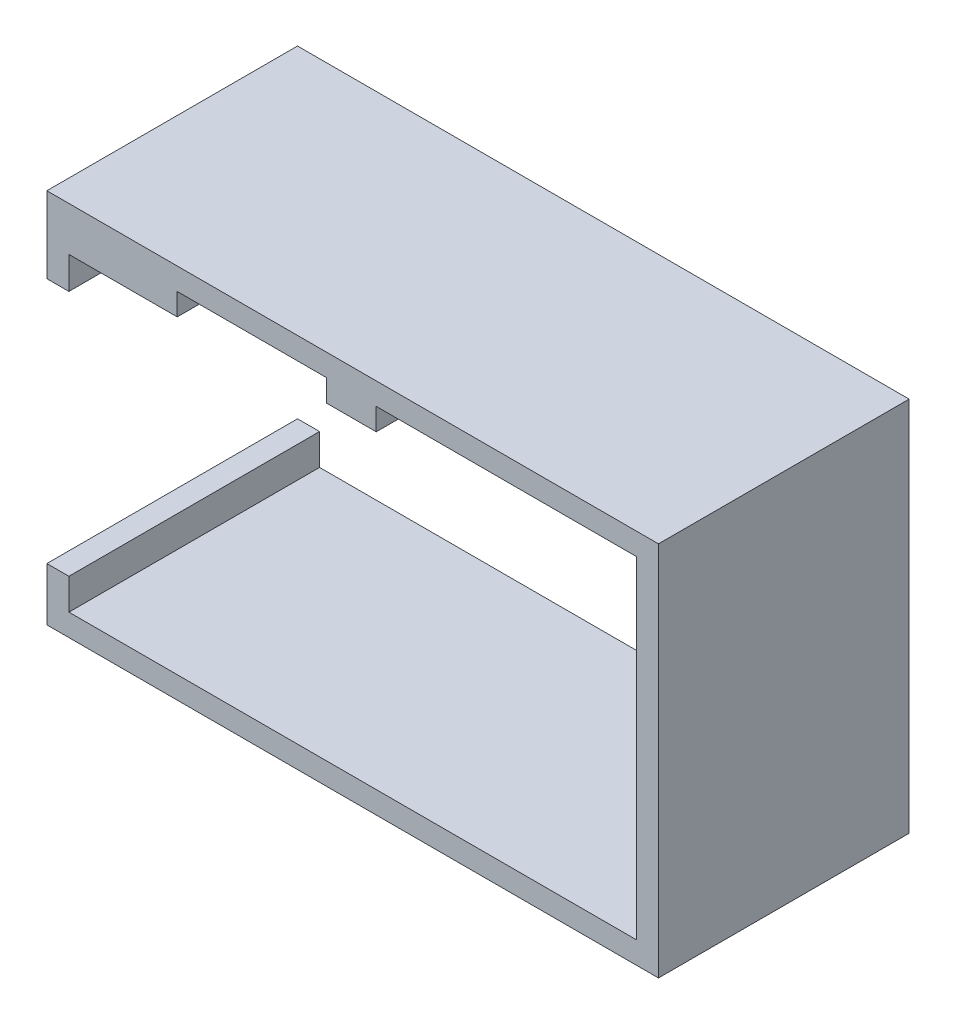
SolidWorks part; units mm, degrees
ref_plane "Front" through (0, 0, 0) normal (0, 0, 1) x (1, 0, 0)
ref_plane "Top" through (0, 0, 0) normal (0, 1, 0) x (1, 0, 0)
ref_plane "Right" through (0, 0, 0) normal (1, 0, 0) x (0, 0, -1)
sketch "Esquisse1" plane through (0, 0, 0) normal (0, 0, 1) x (1, 0, 0)
  line L0 (0, 0) -> (5660, 0)
  line L1 (5660, 0) -> (5660, 3310)
  line L2 (5660, 3310) -> (3065, 3310)
  line L3 (3065, 3310) -> (3065, 3090)
  line L4 (3065, 3090) -> (2570, 3090)
  line L5 (2570, 3090) -> (2570, 3310)
  line L6 (2570, 3310) -> (1080, 3310)
  line L7 (1080, 3310) -> (1080, 3090)
  line L8 (1080, 3090) -> (0, 3090)
  line L9 (0, 3090) -> (0, 2770)
  line L10 (0, 2770) -> (-220, 2770)
  line L11 (-220, 2770) -> (-220, 3530)
  line L12 (-220, 3530) -> (5880, 3530)
  line L13 (5880, 3530) -> (5880, -220)
  line L14 (5880, -220) -> (-220, -220)
  line L15 (-220, -220) -> (-220, 310)
  line L16 (-220, 310) -> (0, 310)
  line L17 (0, 310) -> (0, 0)
  dimension "D1" = 220
  dimension "D2" = 220
  dimension "D3" = 310
  dimension "D4" = 3310
  dimension "D5" = 220
  dimension "D6" = 220
  dimension "D7" = 320
  dimension "D8" = 220
  dimension "D9" = 2595
  dimension "D10" = 495
  dimension "D11" = 1490
  dimension "D12" = 1080
  dimension "D13" = 220
extrude "Boss.-Extru.1" add sketch "Esquisse1" along normal blind 2500
